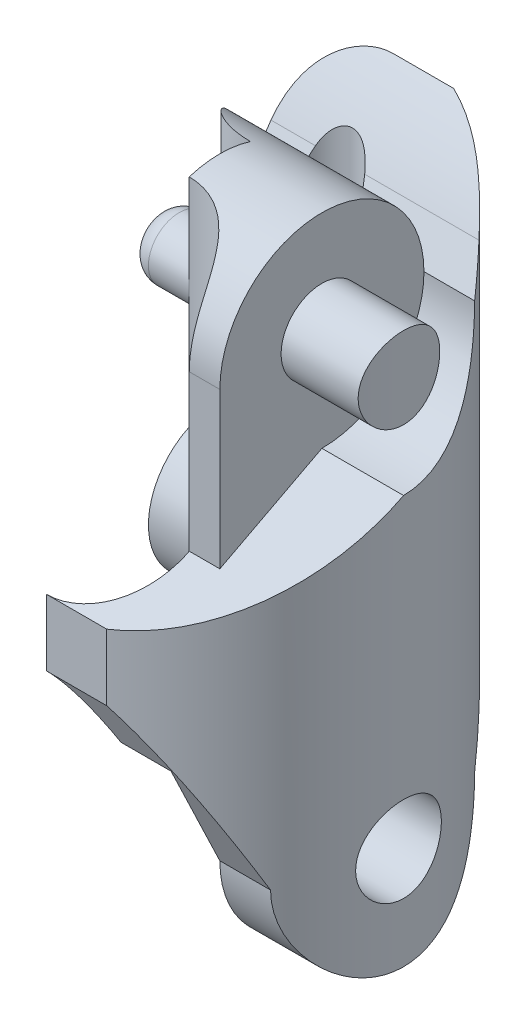
SolidWorks part; units mm, degrees
ref_plane "Front Plane" through (0, 0, 0) normal (0, 0, 1) x (1, 0, 0)
ref_plane "Top Plane" through (0, 0, 0) normal (0, 1, 0) x (1, 0, 0)
ref_plane "Right Plane" through (0, 0, 0) normal (1, 0, 0) x (0, 0, -1)
sketch "Sketch1" plane through (0, 0, 0) normal (0, 1, 0) x (1, 0, 0)
  line L0 (-2.958, 8.5) -> (2.958, 8.5)
  line L1 (-2.958, -8.5) -> (2.958, -8.5)
  arc A0 (-2.958, 8.5) -> (-2.958, -8.5) centre (0, 0) ccw
  arc A1 (2.958, 8.5) -> (2.958, -8.5) centre (0, 0) cw
  point P9 (-9, 0)
  point P10 (9, 0)
  dimension "D1" = 18
  dimension "D2" = 17
extrude "Boss-Extrude1" add sketch "Sketch1" along normal blind 30
sketch "Sketch2" plane through (0, 0, 0) normal (0, -1, 0) x (1, 0, 0)
  line L0 (-1.5, 5) -> (1.5, 5)
  line L1 (-1.5, -5) -> (1.5, -5)
  line L2 (0, 5) -> (0, -5) construction
  arc A2 (-1.5, 5) -> (1.5, 5) centre (0, 5) cw
  arc A3 (-1.5, -5) -> (1.5, -5) centre (0, -5) ccw
  dimension "D1" = 10
  dimension "D2" = 1.5
extrude "Cut-Extrude1" cut sketch "Sketch2" against normal blind 35
sketch "Sketch3" plane through (0, 0, -8.5) normal (0, 0, -1) x (-1, 0, 0)
  line L0 (5, 0) -> (5, 10)
  line L1 (5, 10) -> (-5, 10)
  line L2 (-5, 10) -> (-5, 0)
  line L3 (5, 0) -> (-5, 0)
  line L4 (-2.958, 0) -> (2.958, 0) construction
  point P10 (0, 0)
  dimension "D1" = 10
  dimension "D2" = 10
extrude "Cut-Extrude2" cut sketch "Sketch3" against normal up to surface (17 mm away) up to face at (0, 15, 8.5)
sketch "Sketch4" plane through (5, 0, 0) normal (-1, 0, 0) x (0, 0, 1)
  line L0 (-7.4833, 10) -> (-5, 5)
  line L1 (8.5, 12.3086) -> (5, 5)
  line L2 (7.4833, 0) -> (-7.4833, 0) construction
  line L3 (-7.4833, 10) -> (-9.8579, -1.8222)
  line L4 (-9.8579, -1.8222) -> (9.8579, -1.8222)
  line L6 (8.5, 30) -> (8.5, 10) construction
  line L7 (9.8579, -1.8222) -> (8.5, 12.3086)
  arc A0 (-5, 5) -> (5, 5) centre (0, 5) ccw
  circle A1 centre (0, 5) radius 2.1
  point P7 (0, 0)
  dimension "D1" = 4.2
  dimension "D2" = 5
  dimension "D3" = 12.0584
  dimension "D4" = 37.769
extrude "Cut-Extrude3" cut sketch "Sketch4" against normal mid plane 35
ref_plane "Plane1" through (-2.958, 0, 0) normal (-1, 0, 0) x (0, 0, 1)
sketch "Sketch6" plane through (-2.958, 0, 0) normal (-1, 0, 0) x (0, 0, 1)
  line L0 (8.5, 15.5583) -> (0, 20)
  line L1 (8.5, 30) -> (8.5, 12.3086) construction
  line L2 (-5, 25) -> (-5.8896, 26.7912)
  line L3 (8.5, 30) -> (-8.5, 30) construction
  line L4 (8.5, 15.5583) -> (17.803, 42.886)
  line L6 (-7.4833, 10) -> (-5, 5) construction
  line L7 (-8.5, 30) -> (17.803, 42.886)
  line L8 (5, 5) -> (8.5, 12.3086) construction
  arc A0 (0, 20) -> (-5, 25) centre (0, 25) cw
  circle A1 centre (0, 25) radius 2
  arc A2 (-5.8896, 26.7912) -> (-8.5, 30) centre (-14.3043, 22.612) ccw
  dimension "D1" = 5
  dimension "D3" = 4
  dimension "D2" = 5
  dimension "D4" = 8.5
  dimension "D5" = 2
  dimension "D6" = 92
extrude "Cut-Extrude5" cut sketch "Sketch6" against normal blind 9.6 from surface starting at face at (5, 7.1, 0)
sketch "Sketch7" plane through (5, 0, 0) normal (1, 0, 0) x (0, 0, -1)
  line L0 (5, 25) -> (5.8896, 26.7912)
  line L2 (-8.3419, 47.5367) -> (-34.7491, 41.0454)
  line L3 (-7.4833, 30) -> (7.4833, 30) construction
  line L4 (-5, 25) -> (-5, 17.3872)
  line L5 (-7.4833, 16.0896) -> (0, 20) construction
  line L6 (-5, 17.3872) -> (-17.4521, 10.8804)
  line L7 (-17.4521, 10.8804) -> (-34.7491, 41.0454)
  line L8 (5.8896, 26.7912) -> (5, 25) construction
  line L9 (8.5, 30) -> (-8.3419, 47.5367)
  arc A0 (5, 25) -> (-5, 25) centre (0, 25) ccw
  arc A1 (5.8896, 26.7912) -> (8.5, 30) centre (14.3043, 22.612) cw
  arc A2 (7.4833, 29.0732) -> (5.8896, 26.7912) centre (14.3043, 22.612) ccw construction
  dimension "D1" = 5
fillet "Fillet3" radius 1 4 edges at (0, 10, -6.5) (0, 10, -5) (0, 10, 6.5) (0, 10, 5)
extrude "Cut-Extrude6" cut sketch "Sketch6<3>" along normal blind 6.604 from surface starting at face at (-5, 2.9, 0)
sketch "Sketch6<3>" plane through (-2.958, 0, 0) normal (-1, 0, 0) x (0, 0, 1) same geometry as "Sketch6"
extrude "Cut-Extrude7" cut sketch "Sketch7" against normal blind 14.986
sketch "Sketch8" plane through (0, 10, 0) normal (0, -1, 0) x (1, 0, 0)
  line L0 (0, 1.5) -> (0, -1.5)
  line L1 (-2.958, -8.5) -> (2.958, -8.5) construction
  line L2 (2.958, 8.5) -> (-2.958, 8.5) construction
  line L3 (0, 8.5) -> (-4.7901, 15.219)
  line L4 (-4.7901, 15.219) -> (-17.8556, -9.7177)
  line L5 (-17.8556, -9.7177) -> (-4.7901, -16.0136)
  line L6 (-4.7901, -16.0136) -> (0, -8.5)
  arc A0 (0, -1.5) -> (0, -8.5) centre (0, -5) ccw
  arc A1 (0, 1.5) -> (0, 8.5) centre (0, 5) ccw
  arc A4 (2.2913, 4) -> (0.7187, 7.3945) centre (0, 5) ccw construction
  arc A5 (-2.2913, -4) -> (2.2913, -4) centre (0, -5) ccw construction
extrude "Cut-Extrude8" cut sketch "Sketch8" against normal mid plane 62.992
sketch "Sketch9" plane through (0, 0, 0) normal (-1, 0, 0) x (0, 0, 1)
  line L0 (7.3945, 10) -> (-7.4833, 10) construction
  circle A0 centre (0, 16) radius 1.5
  dimension "D2" = 3
  dimension "D1" = 6
extrude "Cut-Extrude9" cut sketch "Sketch9" against normal blind 8.382
sketch "Sketch11" plane through (0, 0, 0) normal (-1, 0, 0) x (0, 0, 1)
  circle A0 centre (0, 16) radius 2
  dimension "D1" = 4
extrude "Cut-Extrude10" cut sketch "Sketch11" against normal mid plane 6.2
sketch "Sketch12" plane through (0, 0, 0) normal (-1, 0, 0) x (0, 0, 1)
  line L0 (0, 18) -> (0, 19.5)
  line L1 (0, 14) -> (0, 12.5)
  arc A0 (1.5, 17.3229) -> (-1.5, 17.3229) centre (0, 16) ccw construction
  arc A1 (-1.5, 14.6771) -> (1.5, 14.6771) centre (0, 16) ccw construction
  arc A2 (0, 19.5) -> (0, 12.5) centre (0, 16) cw
  arc A3 (1.5, 14.6771) -> (1.5, 17.3229) centre (0, 16) ccw construction
  arc A4 (0, 18) -> (0, 14) centre (0, 16) cw
  dimension "D1" = 1.5
extrude "Boss-Extrude2" add sketch "Sketch12" against normal blind 3.862
sketch "Sketch13" plane through (0, 0, 0) normal (-1, 0, 0) x (0, 0, 1)
  line L0 (1.5, 29.7697) -> (1.5, 19.1623) construction
  circle A0 centre (0, 25) radius 1.5
  circle A1 centre (0, 25) radius 2 construction
extrude "Boss-Extrude4" add sketch "Sketch13" along normal blind 3
fillet "Fillet5" radius 1 1 edges at (-3, 25, 1.5)
